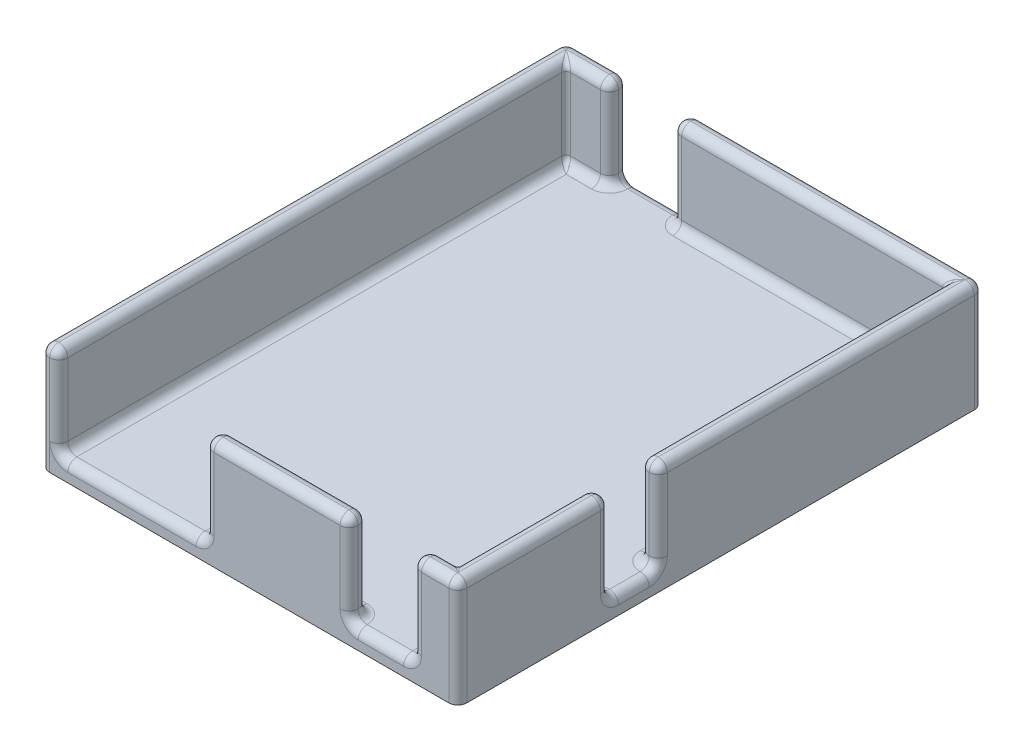
SolidWorks part; units mm, degrees
note: The reader was unsure of these and kept them because the rebuilt part matched: shared geometry of "Sketch2<3>".
ref_plane "Front Plane" through (0, 0, 0) normal (0, 0, 1) x (1, 0, 0)
ref_plane "Top Plane" through (0, 0, 0) normal (0, 1, 0) x (1, 0, 0)
ref_plane "Right Plane" through (0, 0, 0) normal (1, 0, 0) x (0, 0, -1)
sketch "Sketch1" plane through (0, 0, 0) normal (0, 1, 0) x (1, 0, 0)
  line L1 (0, 0) -> (58.674, 0)
  line L2 (0, 0) -> (0, 73.914)
  line L3 (0, 73.914) -> (58.674, 73.914)
  line L4 (58.674, 0) -> (58.674, 73.914)
  dimension "D1" = 58.674
  dimension "D2" = 73.914
extrude "Boss-Extrude1" add sketch "Sketch1" along normal blind 15.24 contours L2 L3 L4 L1
shell "Shell1" thickness 2.54
sketch "Sketch2" plane through (0, 0, -2.54) normal (0, 0, -1) x (-1, 0, 0)
  line L0 (-2.54, 15.24) -> (-56.134, 15.24) construction
  line L1 (-2.54, 2.54) -> (-23.114, 2.54)
  line L2 (-2.54, 2.54) -> (-2.54, 15.24)
  line L3 (-2.54, 15.24) -> (-23.114, 15.24)
  line L4 (-23.114, 2.54) -> (-23.114, 15.24)
  line L5 (-2.54, 2.54) -> (-56.134, 2.54) construction
  line L6 (-52.2986, 2.54) -> (-43.3832, 2.54)
  line L7 (-52.2986, 2.54) -> (-52.2986, 15.24)
  line L8 (-52.2986, 15.24) -> (-43.3832, 15.24)
  line L9 (-43.3832, 2.54) -> (-43.3832, 15.24)
  line L10 (-56.134, 15.24) -> (-56.134, 2.54) construction
  dimension "D1" = 20.574
  dimension "D2" = 8.9154
  dimension "D3" = 3.8354
extrude "Cut-Extrude1" cut sketch "Sketch2" against normal blind 12.7 contours L7 L8 L9 L6
extrude "Cut-Extrude2" cut sketch "Sketch2<3>" against normal blind 12.7
sketch "Sketch2<3>" plane through (0, 0, -2.54) normal (0, 0, -1) x (-1, 0, 0) same geometry as "Sketch2"
sketch "Sketch6" plane through (0, 0, -71.374) normal (0, 0, 1) x (1, 0, 0)
  line L0 (2.54, 2.54) -> (56.134, 2.54) construction
  line L1 (8.636, 2.54) -> (17.526, 2.54)
  line L2 (8.636, 2.54) -> (8.636, 15.24)
  line L3 (8.636, 15.24) -> (17.526, 15.24)
  line L4 (17.526, 2.54) -> (17.526, 15.24)
  line L5 (2.54, 15.24) -> (56.134, 15.24) construction
  line L6 (2.54, 15.24) -> (2.54, 2.54) construction
  dimension "D1" = 8.89
  dimension "D2" = 6.096
extrude "Cut-Extrude3" cut sketch "Sketch6" against normal blind 12.7
sketch "Sketch7" plane through (56.134, 0, 0) normal (-1, 0, 0) x (0, 0, 1)
  line L0 (-2.54, 2.54) -> (-71.374, 2.54) construction
  line L1 (-21.336, 2.54) -> (-28.194, 2.54)
  line L2 (-21.336, 2.54) -> (-21.336, 15.24)
  line L3 (-21.336, 15.24) -> (-28.194, 15.24)
  line L4 (-28.194, 2.54) -> (-28.194, 15.24)
  line L5 (-2.54, 15.24) -> (-71.374, 15.24) construction
  line L6 (-2.54, 15.24) -> (-2.54, 2.54) construction
  dimension "D1" = 18.796
  dimension "D2" = 6.858
extrude "Cut-Extrude4" cut sketch "Sketch7" against normal blind 12.7
fillet "Fillet3" radius 1.27 59 edges at (57.404, 15.24, -28.194) (57.404, 15.24, -21.336) (57.404, 2.54, -21.336) (57.404, 2.54, -28.194) (56.134, 8.89, -21.336) (56.134, 8.89, -28.194) (4.318, 15.24, -73.914) (56.134, 2.54, -11.938) (0, 15.24, -36.957) (5.588, 15.24, -71.374) (2.54, 15.24, -35.687) (56.134, 15.24, -11.938) (2.54, 2.54, -35.687) (5.588, 2.54, -71.374) (55.4863, 15.24, 0) (43.3832, 8.89, 0) (47.8409, 2.54, 0) (52.2986, 8.89, 0) (54.2163, 2.54, -2.54) (54.2163, 15.24, -2.54) (43.3832, 2.54, -1.27) (52.2986, 2.54, -1.27) (52.2986, 8.89, -2.54) (43.3832, 15.24, -1.27) (52.2986, 15.24, -1.27) (43.3832, 8.89, -2.54) (33.2486, 2.54, -2.54) (33.2486, 15.24, 0) (12.827, 2.54, 0) (33.2486, 15.24, -2.54) (23.114, 15.24, -1.27) (2.54, 8.89, 0) (1.27, 15.24, 0) (23.114, 8.89, 0) (23.114, 2.54, -1.27) (23.114, 8.89, -2.54) (38.1, 15.24, -73.914) (13.081, 2.54, -73.914) (17.526, 8.89, -73.914) (8.636, 8.89, -73.914) (36.83, 2.54, -71.374) (0, 7.62, 0) (36.83, 15.24, -71.374) (0, 7.62, -73.914) (58.674, 7.62, -73.914) (58.674, 7.62, 0) (8.636, 2.54, -72.644) (8.636, 15.24, -72.644) (17.526, 15.24, -72.644) (17.526, 2.54, -72.644) (8.636, 8.89, -71.374) (17.526, 8.89, -71.374) (58.674, 15.24, -10.668) (58.674, 15.24, -51.054) (58.674, 8.89, -28.194) (58.674, 2.54, -24.765) (58.674, 8.89, -21.336) (56.134, 2.54, -49.784) (56.134, 15.24, -49.784)
fillet "Fillet4" radius 0.635 9 edges at (56.134, 8.89, -2.54) (2.54, 8.89, -71.374) (56.134, 8.89, -71.374) (2.168, 14.868, -71.746) (2.912, 2.912, -71.002) (56.506, 14.868, -2.168) (55.762, 2.912, -2.912) (55.762, 2.912, -71.002) (56.506, 14.868, -71.746)
